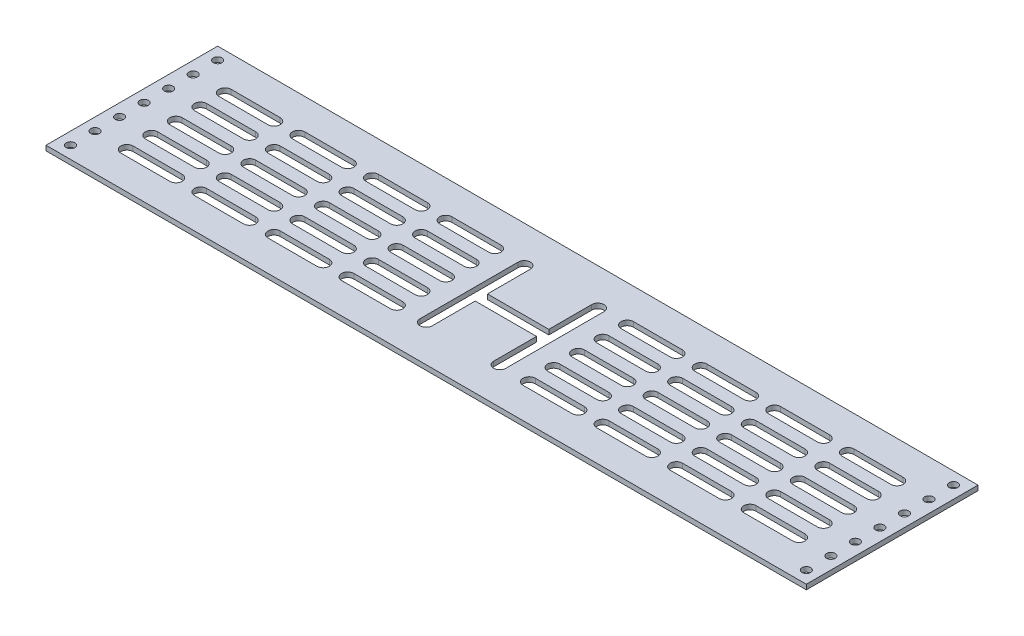
SolidWorks part; units mm, degrees
material "6061 合金"
ref_plane "前视基准面" through (0, 0, 0) normal (0, 0, 1) x (1, 0, 0)
ref_plane "上视基准面" through (0, 0, 0) normal (0, 1, 0) x (1, 0, 0)
ref_plane "右视基准面" through (0, 0, 0) normal (1, 0, 0) x (0, 0, -1)
other "Configuration Table"
sketch "草图1" plane through (0, 0, 0) normal (0, 1, 0) x (1, 0, 0)
  line L0 (0, 0) -> (-155, 0)
  line L1 (0, 0) -> (155, 0)
  line L2 (155, 0) -> (155, -80)
  line L3 (155, -80) -> (-155, -80)
  line L4 (-155, -80) -> (-155, 0)
  dimension "D1" = 155
  dimension "D2" = 80
  dimension "D3" = 155
extrude "凸台-拉伸1" add sketch "草图1" along normal blind 2
sketch "草图2" plane through (0, 2, 0) normal (0, 1, 0) x (1, 0, 0)
  line L0 (-155, -80) -> (-150, -80)
  line L1 (-155, -80) -> (155, -80) construction
  line L2 (-150, -80) -> (-150, 0)
  line L3 (155, 0) -> (-155, 0) construction
  line L4 (-150, -80) -> (-150, -75)
  line L5 (0, 0) -> (0, -80)
  circle A0 centre (-150, -75) radius 1.75
  circle A1 centre (-150, -65) radius 1.75
  circle A2 centre (-150, -55) radius 1.75
  circle A3 centre (-150, -45) radius 1.75
  circle A4 centre (-150, -35) radius 1.75
  circle A5 centre (-150, -25) radius 1.75
  circle A6 centre (-150, -15) radius 1.75
  circle A7 centre (-150, -5) radius 1.75
  circle A8 centre (150, -5) radius 1.75
  circle A9 centre (150, -15) radius 1.75
  circle A10 centre (150, -25) radius 1.75
  circle A11 centre (150, -35) radius 1.75
  circle A12 centre (150, -45) radius 1.75
  circle A13 centre (150, -55) radius 1.75
  circle A14 centre (150, -65) radius 1.75
  circle A15 centre (150, -75) radius 1.75
  dimension "D1" = 8
  dimension "D2" = 3.5
  dimension "D3" = 5
extrude "切除-拉伸1" cut sketch "草图2" against normal through all contours L4 A0 L2 | L2 A0 L4 | L2 A1 | L2 A1 | L2 A2 | L2 A2 | L2 A3 | L2 A3 | L2 A4 | L2 A4 | L2 A5 | L2 A5 | L2 A6 | L2 A6 | L2 A7 | L2 A7 | A8 | A9 | A10 | A11 | A12 | A13 | A14 | A15 region at (-150.7427, 2, 75) region at (-150.7427, 2, 5) region at (-149.2573, 2, 5) region at (-150.7427, 2, 15) region at (-149.2573, 2, 15) region at (-150.7427, 2, 25) region at (-149.2573, 2, 25) region at (-150.7427, 2, 35) region at (-149.2573, 2, 35) region at (-150.7427, 2, 45) region at (-149.2573, 2, 45) region at (-150.7427, 2, 55) region at (-149.2573, 2, 55) region at (-150.7427, 2, 65) region at (-149.2573, 2, 65) region at (-149.2573, 2, 75) region at (150, 2, 5) region at (150, 2, 15) region at (150, 2, 25) region at (150, 2, 35) region at (150, 2, 45) region at (150, 2, 55) region at (150, 2, 65) region at (150, 2, 75)
sketch "草图3" plane through (0, 2, 0) normal (0, 1, 0) x (1, 0, 0)
  line L0 (0, -80) -> (0, -45)
  line L1 (155, 0) -> (-155, 0) construction
  line L2 (-155, -80) -> (155, -80) construction
  line L3 (0, -45) -> (-15, -45)
  line L4 (0, -45) -> (15, -45)
  line L5 (15, -45) -> (15, -25)
  line L6 (15, -45) -> (15, -65)
  line L7 (-15, -45) -> (-15, -25)
  line L8 (-15, -45) -> (-15, -65)
  line L9 (-15, -45) -> (15, -45) construction
  line L10 (-12.5, -42.5) -> (12.5, -42.5)
  line L11 (-12.5, -47.5) -> (12.5, -47.5)
  line L12 (-15, -25) -> (-15, -65) construction
  line L13 (-12.5, -25) -> (-12.5, -42.5)
  line L14 (-17.5, -25) -> (-17.5, -65)
  line L15 (15, -25) -> (15, -65) construction
  line L16 (17.5, -25) -> (17.5, -65)
  line L17 (12.5, -25) -> (12.5, -42.5)
  line L18 (12.5, -47.5) -> (12.5, -65)
  line L19 (-12.5, -47.5) -> (-12.5, -65)
  line L20 (-155, -80) -> (0, -80)
  line L21 (-77.5, -80) -> (-77.5, 0)
  line L22 (-150, -65) -> (-77.5, -65)
  line L25 (-147, -65) -> (-137, -65)
  line L26 (-137, -65) -> (-117, -65)
  line L27 (-117, -65) -> (-107, -65)
  line L28 (-107, -65) -> (-87, -65)
  line L29 (-87, -65) -> (-77, -65)
  line L30 (-77, -65) -> (-57, -65)
  line L34 (-137, -65) -> (-117, -65) construction
  line L35 (-137, -62.5) -> (-117, -62.5)
  line L36 (-137, -67.5) -> (-117, -67.5)
  line L37 (-107, -65) -> (-87, -65) construction
  line L38 (-107, -62.5) -> (-87, -62.5)
  line L39 (-107, -67.5) -> (-87, -67.5)
  line L40 (-77, -65) -> (-57, -65) construction
  line L41 (-77, -62.5) -> (-57, -62.5)
  line L42 (-77, -67.5) -> (-57, -67.5)
  line L45 (-137, -57.5) -> (-117, -57.5)
  line L46 (-137, -52.5) -> (-117, -52.5)
  line L47 (-107, -57.5) -> (-87, -57.5)
  line L48 (-107, -52.5) -> (-87, -52.5)
  line L49 (-77, -57.5) -> (-57, -57.5)
  line L50 (-77, -52.5) -> (-57, -52.5)
  line L52 (-137, -55) -> (-117, -55) construction
  line L53 (-107, -55) -> (-87, -55) construction
  line L54 (-77, -55) -> (-57, -55) construction
  line L57 (-137, -47.5) -> (-117, -47.5)
  line L58 (-137, -42.5) -> (-117, -42.5)
  line L59 (-107, -47.5) -> (-87, -47.5)
  line L60 (-107, -42.5) -> (-87, -42.5)
  line L61 (-77, -47.5) -> (-57, -47.5)
  line L62 (-77, -42.5) -> (-57, -42.5)
  line L64 (-137, -45) -> (-117, -45) construction
  line L65 (-107, -45) -> (-87, -45) construction
  line L66 (-77, -45) -> (-57, -45) construction
  line L69 (-137, -37.5) -> (-117, -37.5)
  line L70 (-137, -32.5) -> (-117, -32.5)
  line L71 (-107, -37.5) -> (-87, -37.5)
  line L72 (-107, -32.5) -> (-87, -32.5)
  line L73 (-77, -37.5) -> (-57, -37.5)
  line L74 (-77, -32.5) -> (-57, -32.5)
  line L76 (-137, -35) -> (-117, -35) construction
  line L77 (-107, -35) -> (-87, -35) construction
  line L78 (-77, -35) -> (-57, -35) construction
  line L99 (-147, -25) -> (-137, -25)
  line L100 (-137, -25) -> (-117, -25)
  line L101 (-117, -25) -> (-107, -25)
  line L102 (-107, -25) -> (-87, -25)
  line L109 (-87, -25) -> (-77, -25)
  line L112 (-77, -25) -> (-57, -25)
  line L115 (-57, -25) -> (-47, -25)
  line L118 (-47, -25) -> (-27, -25)
  line L178 (-137, -25) -> (-117, -25) construction
  line L181 (-57, -65) -> (-47, -65)
  line L182 (-47, -65) -> (-27, -65)
  line L183 (-47, -65) -> (-27, -65) construction
  line L184 (-47, -62.5) -> (-27, -62.5)
  line L185 (-47, -67.5) -> (-27, -67.5)
  line L186 (-47, -57.5) -> (-27, -57.5)
  line L187 (-47, -52.5) -> (-27, -52.5)
  line L188 (-47, -55) -> (-27, -55) construction
  line L189 (-47, -47.5) -> (-27, -47.5)
  line L190 (-47, -42.5) -> (-27, -42.5)
  line L191 (-47, -45) -> (-27, -45) construction
  line L192 (-47, -37.5) -> (-27, -37.5)
  line L193 (-47, -32.5) -> (-27, -32.5)
  line L194 (-47, -35) -> (-27, -35) construction
  line L197 (-137, -22.5) -> (-117, -22.5)
  line L200 (-137, -27.5) -> (-117, -27.5)
  line L202 (-107, -25) -> (-87, -25) construction
  line L205 (-107, -22.5) -> (-87, -22.5)
  line L222 (-137, -22.5) -> (-117, -22.5) [skipped]
  line L223 (-137, -27.5) -> (-117, -27.5) [skipped]
  line L224 (-107, -22.5) -> (-87, -22.5) [skipped]
  line L225 (-107, -27.5) -> (-87, -27.5) [skipped]
  line L226 (-77, -22.5) -> (-57, -22.5) [skipped]
  line L227 (-77, -27.5) -> (-57, -27.5) [skipped]
  line L230 (-137, -12.5) -> (-117, -12.5) [skipped]
  line L231 (-137, -17.5) -> (-117, -17.5) [skipped]
  line L232 (-107, -12.5) -> (-87, -12.5) [skipped]
  line L233 (-107, -17.5) -> (-87, -17.5) [skipped]
  line L234 (-77, -12.5) -> (-57, -12.5) [skipped]
  line L235 (-77, -17.5) -> (-57, -17.5) [skipped]
  line L236 (-47, -22.5) -> (-27, -22.5) [skipped]
  line L237 (-47, -27.5) -> (-27, -27.5) [skipped]
  line L238 (-47, -12.5) -> (-27, -12.5) [skipped]
  line L239 (-47, -17.5) -> (-27, -17.5) [skipped]
  line L240 (-107, -27.5) -> (-87, -27.5)
  line L241 (-77, -25) -> (-57, -25) construction
  line L242 (-77, -22.5) -> (-57, -22.5)
  line L243 (-77, -27.5) -> (-57, -27.5)
  line L244 (-47, -25) -> (-27, -25) construction
  line L245 (-47, -22.5) -> (-27, -22.5)
  line L246 (-47, -27.5) -> (-27, -27.5)
  arc A2 (-12.5, -25) -> (-17.5, -25) centre (-15, -25) ccw
  arc A3 (-17.5, -65) -> (-12.5, -65) centre (-15, -65) ccw
  arc A4 (17.5, -25) -> (12.5, -25) centre (15, -25) ccw
  arc A5 (12.5, -65) -> (17.5, -65) centre (15, -65) ccw
  arc A8 (-137, -62.5) -> (-137, -67.5) centre (-137, -65) ccw
  arc A9 (-117, -67.5) -> (-117, -62.5) centre (-117, -65) ccw
  arc A10 (-107, -62.5) -> (-107, -67.5) centre (-107, -65) ccw
  arc A11 (-87, -67.5) -> (-87, -62.5) centre (-87, -65) ccw
  arc A12 (-77, -62.5) -> (-77, -67.5) centre (-77, -65) ccw
  arc A13 (-57, -67.5) -> (-57, -62.5) centre (-57, -65) ccw
  arc A16 (-137, -52.5) -> (-137, -57.5) centre (-137, -55) ccw
  arc A17 (-117, -57.5) -> (-117, -52.5) centre (-117, -55) ccw
  arc A18 (-107, -52.5) -> (-107, -57.5) centre (-107, -55) ccw
  arc A19 (-87, -57.5) -> (-87, -52.5) centre (-87, -55) ccw
  arc A20 (-77, -52.5) -> (-77, -57.5) centre (-77, -55) ccw
  arc A21 (-57, -57.5) -> (-57, -52.5) centre (-57, -55) ccw
  arc A24 (-137, -42.5) -> (-137, -47.5) centre (-137, -45) ccw
  arc A25 (-117, -47.5) -> (-117, -42.5) centre (-117, -45) ccw
  arc A26 (-107, -42.5) -> (-107, -47.5) centre (-107, -45) ccw
  arc A27 (-87, -47.5) -> (-87, -42.5) centre (-87, -45) ccw
  arc A28 (-77, -42.5) -> (-77, -47.5) centre (-77, -45) ccw
  arc A29 (-57, -47.5) -> (-57, -42.5) centre (-57, -45) ccw
  arc A32 (-137, -32.5) -> (-137, -37.5) centre (-137, -35) ccw
  arc A33 (-117, -37.5) -> (-117, -32.5) centre (-117, -35) ccw
  arc A34 (-107, -32.5) -> (-107, -37.5) centre (-107, -35) ccw
  arc A35 (-87, -37.5) -> (-87, -32.5) centre (-87, -35) ccw
  arc A36 (-77, -32.5) -> (-77, -37.5) centre (-77, -35) ccw
  arc A37 (-57, -37.5) -> (-57, -32.5) centre (-57, -35) ccw
  arc A102 (-47, -62.5) -> (-47, -67.5) centre (-47, -65) ccw
  arc A103 (-27, -67.5) -> (-27, -62.5) centre (-27, -65) ccw
  arc A104 (-47, -52.5) -> (-47, -57.5) centre (-47, -55) ccw
  arc A105 (-27, -57.5) -> (-27, -52.5) centre (-27, -55) ccw
  arc A106 (-47, -42.5) -> (-47, -47.5) centre (-47, -45) ccw
  arc A107 (-27, -47.5) -> (-27, -42.5) centre (-27, -45) ccw
  arc A108 (-47, -32.5) -> (-47, -37.5) centre (-47, -35) ccw
  arc A109 (-27, -37.5) -> (-27, -32.5) centre (-27, -35) ccw
  arc A128 (-137, -22.5) -> (-137, -27.5) centre (-137, -25) ccw [skipped]
  arc A129 (-117, -27.5) -> (-117, -22.5) centre (-117, -25) ccw [skipped]
  arc A130 (-107, -22.5) -> (-107, -27.5) centre (-107, -25) ccw [skipped]
  arc A131 (-87, -27.5) -> (-87, -22.5) centre (-87, -25) ccw [skipped]
  arc A132 (-77, -22.5) -> (-77, -27.5) centre (-77, -25) ccw [skipped]
  arc A133 (-57, -27.5) -> (-57, -22.5) centre (-57, -25) ccw [skipped]
  arc A136 (-137, -12.5) -> (-137, -17.5) centre (-137, -15) ccw [skipped]
  arc A137 (-117, -17.5) -> (-117, -12.5) centre (-117, -15) ccw [skipped]
  arc A138 (-107, -12.5) -> (-107, -17.5) centre (-107, -15) ccw [skipped]
  arc A139 (-87, -17.5) -> (-87, -12.5) centre (-87, -15) ccw [skipped]
  arc A140 (-77, -12.5) -> (-77, -17.5) centre (-77, -15) ccw [skipped]
  arc A141 (-57, -17.5) -> (-57, -12.5) centre (-57, -15) ccw [skipped]
  arc A142 (-47, -22.5) -> (-47, -27.5) centre (-47, -25) ccw [skipped]
  arc A143 (-27, -27.5) -> (-27, -22.5) centre (-27, -25) ccw [skipped]
  arc A144 (-47, -12.5) -> (-47, -17.5) centre (-47, -15) ccw [skipped]
  arc A145 (-27, -17.5) -> (-27, -12.5) centre (-27, -15) ccw [skipped]
  arc A148 (-137, -22.5) -> (-137, -27.5) centre (-137, -25) ccw
  arc A149 (-117, -27.5) -> (-117, -22.5) centre (-117, -25) ccw
  arc A150 (-107, -22.5) -> (-107, -27.5) centre (-107, -25) ccw
  arc A151 (-87, -27.5) -> (-87, -22.5) centre (-87, -25) ccw
  arc A152 (-77, -22.5) -> (-77, -27.5) centre (-77, -25) ccw
  arc A153 (-57, -27.5) -> (-57, -22.5) centre (-57, -25) ccw
  arc A154 (-47, -22.5) -> (-47, -27.5) centre (-47, -25) ccw
  arc A155 (-27, -27.5) -> (-27, -22.5) centre (-27, -25) ccw
  point P8 (0, -40)
  point P18 (-15, -40)
  point P23 (15, -40)
  point P48 (-127, -65)
  point P53 (-97, -65)
  point P58 (-67, -65)
  point P78 (-127, -55)
  point P83 (-97, -55)
  point P88 (-67, -55)
  point P106 (-127, -45)
  point P111 (-97, -45)
  point P116 (-67, -45)
  point P134 (-127, -35)
  point P139 (-97, -35)
  point P144 (-67, -35)
  point P166 (-127, -25)
  point P171 (-97, -25)
  point P176 (-67, -25)
  point P181 (-37, -25)
  point P374 (-37, -65)
  point P383 (-37, -55)
  point P390 (-37, -45)
  point P397 (-37, -35)
  dimension "D3" = 6
  dimension "D4" = 6
  dimension "D1" = 15
  dimension "D2" = 35
  dimension "D5" = 20
  dimension "D6" = 15
  dimension "D7" = 20
sketch "草图4" plane through (0, 0, 0) normal (0, -1, 0) x (1, 0, 0)
  line L0 (150, 15) -> (150, 10)
  line L1 (150, 10) -> (187.2333, 10)
  line L2 (155, 0) -> (168.6166, 10)
  line L3 (168.6166, 10) -> (-155, 10)
  line L4 (-155, 0) -> (-155, 80) construction
  line L5 (-155, 10) -> (-155, 0)
  line L6 (-155, 0) -> (155, 0)
extrude "切除-拉伸3" cut sketch "草图4" against normal blind 10 contours L5 L6 L2 L1 L3 region at (3.4285, 0, 5.0358)
extrude "切除-拉伸4" cut sketch "草图3" against normal blind 10 contours L200 A149 L101 L100 L99 A148 | L101 A149 L197 A148 L99 L100 | L240 A151 L109 L102 L101 A150 | L109 A151 L205 A150 L101 L102 | L69 A33 L70 A32 | L57 A25 L58 A24 | L45 A17 L46 A16 | L22 A9 L35 A8 L25 | L22 A11 L38 A10 | L47 A19 L48 A18 | L59 A27 L60 A26 | L71 A35 L72 A34 | L36 A9 L22 L25 A8 | L39 A11 L22 A10 | L21 A152 L109 | L109 A152 L21 | L243 A153 L115 L112 L109 L21 A152 | L115 A153 L242 A152 L21 L109 L112 | L73 A37 L74 A36 L21 | L21 A36 | L61 A29 L62 A28 L21 | L21 A28 | L192 A109 L193 A108 | L189 A107 L190 A106 | L246 A155 L245 A154 | L49 A21 L50 A20 L21 | L186 A105 L187 A104 | L42 A13 L181 L30 L29 L21 A12 | L185 A103 L184 A102 | L181 A13 L41 A12 L21 L29 L30 | L22 A12 L21 | L21 A12 L22 | L21 A20 | L18 A5 L16 A4 L17 L10 L13 A2 L14 A3 L19 L11 region at (-6.25, 2, 46.9299) region at (-127, 2, 66.219) region at (-127, 2, 63.781) region at (-97, 2, 66.219) region at (-97, 2, 63.781) region at (-127, 2, 26.219) region at (-127, 2, 23.781) region at (-97, 2, 26.219) region at (-97, 2, 23.781) region at (-48.5875, 2, 23.4125) region at (-78.3359, 2, 25.9999) region at (-66.2597, 2, 26.2333) region at (-78.3359, 2, 35) region at (-66.2597, 2, 35) region at (-78.3359, 2, 45) region at (-66.2597, 2, 45) region at (-78.3359, 2, 55) region at (-66.2597, 2, 55) region at (-48.5875, 2, 63.4125) region at (-78.3359, 2, 65.9999) region at (-66.2597, 2, 66.2333) region at (-78.3359, 2, 64.0001) region at (-66.2597, 2, 63.7667) region at (-78.3359, 2, 24.0001) region at (-66.2597, 2, 23.7667) region at (-127, 2, 55) region at (-97, 2, 55) region at (-127, 2, 45) region at (-97, 2, 45) region at (-127, 2, 35) region at (-97, 2, 35) region at (-37, 2, 55) region at (-37, 2, 45) region at (-37, 2, 35)
mirror "镜向1" about plane through (0, 0, 0) normal (1, 0, 0) of "切除-拉伸4"
